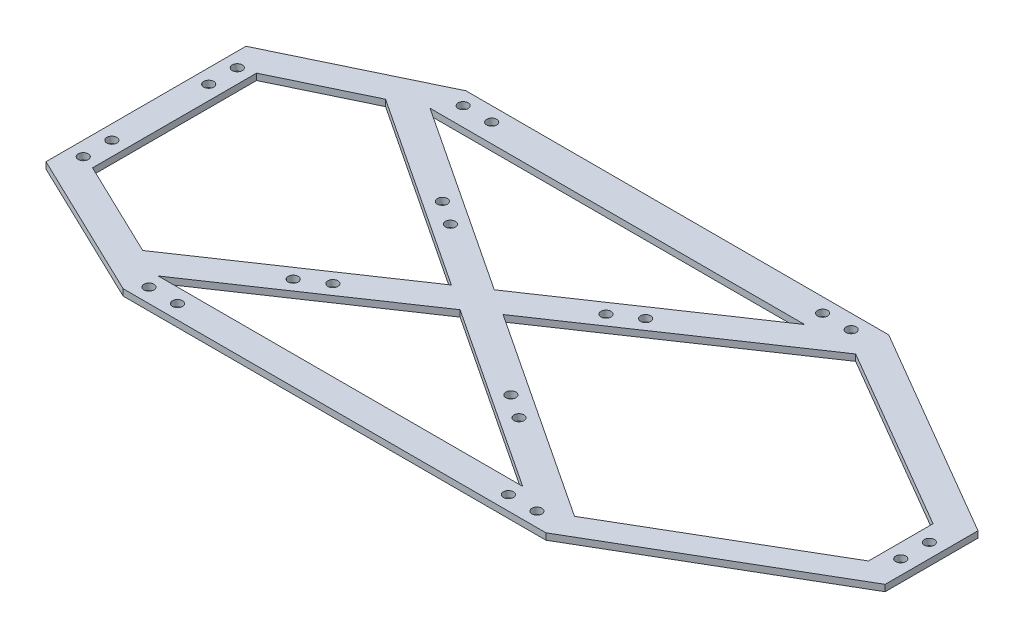
SolidWorks part; units mm, degrees
ref_plane "Front Plane" through (0, 0, 0) normal (0, 0, 1) x (1, 0, 0)
ref_plane "Top Plane" through (0, 0, 0) normal (0, 1, 0) x (1, 0, 0)
ref_plane "Right Plane" through (0, 0, 0) normal (1, 0, 0) x (0, 0, -1)
sketch "Sketch1" plane through (0, 0, 0) normal (0, 1, 0) x (1, 0, 0)
  line L0 (0, 0) -> (0, 120)
  line L1 (0, 120) -> (150, 32.5)
  line L2 (150, 32.5) -> (150, -32.5)
  line L3 (150, -32.5) -> (0, -120)
  line L4 (0, -120) -> (0, 0)
  line L5 (0, 120) -> (-296, 120)
  line L6 (-296, 120) -> (-400, 70)
  line L7 (-400, 70) -> (-400, -70)
  line L8 (-400, -70) -> (-296, -120)
  line L9 (-296, -120) -> (0, -120)
  line L10 (0, 0) -> (150, 0)
  line L11 (0, 0) -> (-400, 0)
  line L12 (-380, 57.424) -> (-298.0025, 96.8459)
  line L13 (-298.0025, 96.8459) -> (0, 96.8459)
  line L14 (0, 96.8459) -> (130, 21.0126)
  line L15 (130, 21.0126) -> (130, -24.1667)
  line L16 (130, -24.1667) -> (0, -100)
  line L17 (0, -100) -> (-291.442, -100)
  line L18 (-291.442, -100) -> (-380, -57.424)
  line L19 (-380, -57.424) -> (-380, 57.424)
  line L20 (-298.0025, 96.8459) -> (0, -100)
  line L21 (0, 96.8459) -> (-291.442, -100)
  line L22 (-319.0039, 86.7491) -> (-36.2869, -100)
  line L23 (-312.3162, -89.9643) -> (-35.7326, 96.8459)
  dimension "D1" = 400
  dimension "D2" = 150
  dimension "D3" = 65
  dimension "D4" = 104
  dimension "D5" = 140
  dimension "D6" = 87.5
  dimension "D7" = 20
  dimension "D8" = 20
  dimension "D9" = 20
  dimension "D10" = 20
  dimension "D11" = 20
  dimension "D12" = 20
  dimension "D13" = 20
  dimension "D14" = 20
extrude "Boss-Extrude3" add sketch "Sketch1" along normal blind 4.5 contours L22 L23 L11 | L23 L11 L20 | L23 L22 L21 L20 L11 | L21 L11 L20 | L23 L20 L11 L21 L13 | L21 L22 L17 L20 | L11 L23 L20 L12 L22 | L23 L18 L21 L22 | L18 L19 L11 L7 L8 L9 L4 L17 | L15 L16 L4 L3 L2 L10 | L14 L15 L10 L2 L1 L0 | L11 L19 L12 L13 L0 L5 L6 L7 region at (-17.8663, 0, -101.022) region at (-86.6407, 0, -50.1699) region at (80.122, 0, -60.1144) region at (81.9637, 0, 60.0667) region at (-4.1761, 0, 110) region at (-86.9285, 0, 54.2987) region at (-147.3726, 0, 0.8908) region at (-165.3635, 0, 5.2316) region at (-165.3052, 0, -3.0868) region at (-241.6998, 0, -47.6632) region at (-238.1338, 0, 51.883) region at (-183.3813, 0, 0.9525)
sketch "Sketch2" plane through (0, 4.5, 0) normal (0, 1, 0) x (1, 0, 0)
  line L0 (-36.2869, -110) -> (-16.2869, -110)
  line L1 (-36.2869, -100) -> (-36.2869, -110)
  circle A0 centre (-16.2869, -110) radius 3.5
  circle A1 centre (-36.2869, -110) radius 3.5
  dimension "D1" = 7
  dimension "D2" = 7
  dimension "D3" = 10
  dimension "D4" = 20
extrude "Cut-Extrude2" cut sketch "Sketch2" against normal blind 4.5 contours L1 A1 L0 | L0 A1 L1 | A0 region at (-34.8015, 4.5, 108.5146) region at (-36.7821, 4.5, 110.4951) region at (-16.2869, 4.5, 106.599)
mirror "Mirror1" about plane through (0, 0, 0) normal (0, 0, 1) of "Cut-Extrude2"
sketch "Sketch3" plane through (0, 4.5, 0) normal (0, 1, 0) x (1, 0, 0)
  line L0 (-287.942, -110) -> (-267.942, -110)
  line L1 (-267.942, -110) -> (-267.942, -100)
  line L2 (-36.2869, -100) -> (-291.442, -100) construction
  line L3 (-291.442, -100) -> (-291.442, -110)
  circle A0 centre (-287.942, -110) radius 3.5
  circle A1 centre (-267.942, -110) radius 3.5
  dimension "D2" = 7
  dimension "D3" = 7
  dimension "D1" = 10
  dimension "D4" = 20
extrude "Cut-Extrude3" cut sketch "Sketch3" against normal blind 4.5 contours L0 A1 L1 | L1 A1 L0 | A0 region at (-269.4275, 4.5, 108.5146) region at (-267.4469, 4.5, 110.4951) region at (-287.942, 4.5, 113.401)
mirror "Mirror2" about plane through (0, 0, 0) normal (0, 0, 1) of "Cut-Extrude3"
sketch "Sketch4" plane through (0, 4.5, 0) normal (0, 1, 0) x (1, 0, 0)
  line L0 (140, 8.423) -> (140, -11.577)
  line L1 (140, -1.577) -> (130, -1.577)
  line L2 (130, 21.0126) -> (130, -24.1667) construction
  circle A0 centre (140, 8.423) radius 3.5
  circle A1 centre (140, -11.577) radius 3.5
  dimension "D1" = 7
  dimension "D2" = 7
  dimension "D3" = 10
  dimension "D4" = 20
extrude "Cut-Extrude4" cut sketch "Sketch4" against normal blind 4.5 contours A0 | A1 region at (142.4049, 4.5, 9.1722) region at (137.5951, 4.5, -10.8278)
sketch "Sketch5" plane through (0, 4.5, 0) normal (0, 1, 0) x (1, 0, 0)
  line L0 (-380, 57.424) -> (-390, 57.424)
  line L1 (-390, 53.924) -> (-390, 33.924)
  circle A0 centre (-390, 53.924) radius 3.5
  circle A1 centre (-390, 33.924) radius 3.5
  dimension "D2" = 7
  dimension "D3" = 7
  dimension "D1" = 10
  dimension "D4" = 20
extrude "Cut-Extrude5" cut sketch "Sketch5" against normal blind 4.5 contours A0 | A1 region at (-387.5951, 4.5, -36.3289) region at (-393.401, 4.5, -53.924)
mirror "Mirror3" about plane through (0, 0, 0) normal (0, 0, 1) of "Cut-Extrude5"
sketch "Sketch6" plane through (0, 4.5, 0) normal (0, 1, 0) x (1, 0, 0)
  line L0 (-220.5289, 33.686) -> (-237.2169, 44.7092)
  line L1 (-237.2169, 44.7092) -> (-231.7053, 53.0532)
  line L2 (-298.0025, 96.8459) -> (-165.408, 9.2605) construction
  circle A0 centre (-237.2169, 44.7092) radius 3.5
  circle A1 centre (-220.5289, 33.686) radius 3.5
  dimension "D3" = 7
  dimension "D4" = 7
  dimension "D1" = 10
  dimension "D2" = 20
extrude "Cut-Extrude6" cut sketch "Sketch6" against normal blind 4.5 contours L1 A0 L0 | L0 A0 L1 | A1 region at (-237.9029, 4.5, -44.569) region at (-235.1587, 4.5, -45.13) region at (-219.5503, 4.5, -36.9431)
sketch "Sketch7" plane through (0, 4.5, 0) normal (0, 1, 0) x (1, 0, 0)
  line L0 (-247.8329, -46.4109) -> (-242.2358, -54.6978)
  line L1 (-312.3162, -89.9643) -> (-183.3496, -2.8576) construction
  line L2 (-242.2358, -54.6978) -> (-225.662, -43.5036)
  circle A0 centre (-242.2358, -54.6978) radius 3.5
  circle A1 centre (-225.662, -43.5036) radius 3.5
  dimension "D3" = 7
  dimension "D4" = 7
  dimension "D1" = 10
  dimension "D2" = 20
extrude "Cut-Extrude7" cut sketch "Sketch7" against normal blind 4.5 contours L0 A0 L2 | L2 A0 L0 | A1 region at (-241.8362, 4.5, 52.6354) region at (-226.6574, 4.5, 40.2515) region at (-242.369, 4.5, 55.3853)
sketch "Sketch8" plane through (0, 4.5, 0) normal (0, 1, 0) x (1, 0, 0)
  line L0 (-100.5703, 53.0532) -> (-94.9732, 44.7663)
  line L1 (-165.408, 9.2605) -> (-35.7326, 96.8459) construction
  line L2 (-94.9732, 44.7663) -> (-111.547, 33.5721)
  circle A0 centre (-94.9732, 44.7663) radius 3.5
  circle A1 centre (-111.547, 33.5721) radius 3.5
  point P7 (-100.5703, 53.0532)
  dimension "D3" = 7
  dimension "D4" = 7
  dimension "D1" = 10
  dimension "D2" = 20
extrude "Cut-Extrude8" cut sketch "Sketch8" against normal blind 4.5 contours L2 A0 L0 | L0 A0 L2 | A1 region at (-94.2858, 4.5, -44.6332) region at (-108.2949, 4.5, -34.5675) region at (-97.0356, 4.5, -45.1659)
sketch "Sketch9" plane through (0, 4.5, 0) normal (0, 1, 0) x (1, 0, 0)
  line L0 (-73.6714, -51.3362) -> (-79.1831, -59.6802)
  line L1 (-147.3429, -2.6725) -> (0, -100) construction
  line L2 (-79.1831, -59.6802) -> (-95.871, -48.657)
  circle A0 centre (-95.871, -48.657) radius 3.5
  circle A1 centre (-79.1831, -59.6802) radius 3.5
  dimension "D3" = 7
  dimension "D4" = 7
  dimension "D1" = 10
  dimension "D2" = 20
extrude "Cut-Extrude9" cut sketch "Sketch9" against normal blind 4.5 contours A0 | L2 A1 L0 | L0 A1 L2 region at (-79.0428, 4.5, 60.3663) region at (-99.1282, 4.5, 47.6783) region at (-79.6038, 4.5, 57.622)
sketch "Sketch10" plane through (0, 4.5, 0) normal (0, 1, 0) x (1, 0, 0)
  line L0 (-400, 70) -> (-400, -70) construction
  line L1 (-400, 0) -> (150, 0)
  line L2 (150, 32.5) -> (150, -32.5) construction
